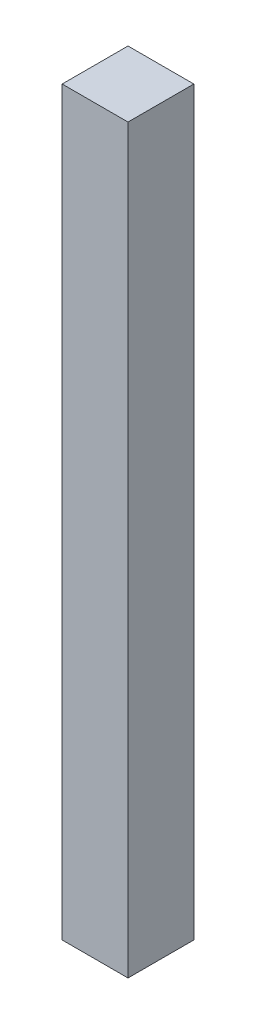
SolidWorks part; units mm, degrees
ref_plane "Front Plane" through (0, 0, 0) normal (0, 0, 1) x (1, 0, 0)
ref_plane "Top Plane" through (0, 0, 0) normal (0, 1, 0) x (1, 0, 0)
ref_plane "Right Plane" through (0, 0, 0) normal (1, 0, 0) x (0, 0, -1)
sketch "Sketch1" plane through (0, 0, 0) normal (0, 1, 0) x (1, 0, 0)
  line L1 (0, 0) -> (25.4, 0)
  line L2 (0, 0) -> (0, 25.4)
  line L3 (0, 25.4) -> (25.4, 25.4)
  line L4 (25.4, 0) -> (25.4, 25.4)
  dimension "D1" = 25.4
  dimension "D2" = 25.4
extrude "Boss-Extrude1" add sketch "Sketch1" along normal blind 609.6
sketch "Sketch3" plane through (0, 0, -25.4) normal (0, 0, -1) x (-1, 0, 0)
  line L0 (0, 609.6) -> (0, 0) construction
  line L1 (0, 466.3042) -> (-25.4, 466.3042)
  line L2 (0, 466.3042) -> (0, 609.6)
  line L3 (0, 609.6) -> (-25.4, 609.6)
  line L4 (-25.4, 466.3042) -> (-25.4, 609.6)
  line L6 (-25.4, 466.3042) -> (0, 466.3042) construction
extrude "Cut-Extrude1" [suppressed] cut sketch "Sketch3" against normal up to surface (25.4 mm away) up to face at (12.7, 304.8, 0)
sketch "Sketch4" [suppressed] plane through (0, 0, 0) normal (0, 0, 1) x (1, 0, 0)
  line L0 (0, 609.6) -> (0, 0) construction
  line L1 (0, 276.4933) -> (25.4, 276.4933)
  line L2 (0, 276.4933) -> (0, 609.6)
  line L3 (0, 609.6) -> (25.4, 609.6)
  line L4 (25.4, 276.4933) -> (25.4, 609.6)
  line L6 (0, 276.4933) -> (25.4, 276.4933) construction
extrude "Cut-Extrude2" [suppressed] cut sketch "Sketch4" against normal up to surface (430.6021 mm away) up to face at (12.7, 304.8, -25.4)
sketch "Sketch5" plane through (0, 0, -25.4) normal (0, 0, -1) x (-1, 0, 0)
  line L0 (0, 609.6) -> (0, 0) construction
  line L1 (0, 571.9407) -> (-25.4, 571.9407)
  line L2 (0, 571.9407) -> (0, 609.6)
  line L3 (0, 609.6) -> (-25.4, 609.6)
  line L4 (-25.4, 571.9407) -> (-25.4, 609.6)
extrude "Cut-Extrude3" cut sketch "Sketch5" against normal up to surface (25.4 mm away) up to face at (12.7, 304.8, 0)
sketch "Sketch6" [suppressed] plane through (0, 0, -25.4) normal (0, 0, -1) x (-1, 0, 0)
  line L0 (0, 609.6) -> (0, 0) construction
  line L1 (0, 553.696) -> (-25.4, 553.696)
  line L2 (0, 553.696) -> (0, 609.6)
  line L3 (0, 609.6) -> (-25.4, 609.6)
  line L4 (-25.4, 553.696) -> (-25.4, 609.6)
  line L6 (-25.4, 553.696) -> (0, 553.696) construction
extrude "Cut-Extrude4" [suppressed] cut sketch "Sketch6" against normal up to surface (25.4 mm away) up to face at (12.7, 285.9703, 0)
sketch "Sketch7" [suppressed] plane through (0, 0, 0) normal (0, 0, 1) x (1, 0, 0)
  line L0 (25.4, 609.6) -> (25.4, 0) construction
  line L1 (25.4, 422.1079) -> (0, 422.1079)
  line L2 (25.4, 422.1079) -> (25.4, 609.6)
  line L3 (25.4, 609.6) -> (0, 609.6)
  line L4 (0, 422.1079) -> (0, 609.6)
  line L8 (0, 422.1079) -> (25.4, 422.1079) construction
extrude "Cut-Extrude5" [suppressed] cut sketch "Sketch7" against normal up to surface (25.4 mm away) up to face at (12.7, 285.9703, -25.4)
sketch "Sketch8" [suppressed] plane through (0, 0, -25.4) normal (0, 0, -1) x (-1, 0, 0)
  line L0 (0, 609.6) -> (0, 0) construction
  line L1 (0, 319.3022) -> (-25.4, 319.3022)
  line L2 (0, 319.3022) -> (0, 609.6)
  line L3 (0, 609.6) -> (-25.4, 609.6)
  line L4 (-25.4, 319.3022) -> (-25.4, 609.6)
  line L6 (-25.4, 319.3022) -> (0, 319.3022) construction
extrude "Cut-Extrude6" [suppressed] cut sketch "Sketch8" against normal up to surface (25.4 mm away) up to face at (12.7, 285.9703, 0)
sketch "Sketch9" [suppressed] plane through (0, 0, 0) normal (0, 0, 1) x (1, 0, 0)
  line L0 (0, 609.6) -> (0, 0) construction
  line L1 (0, 329.8783) -> (25.4, 329.8783)
  line L2 (0, 329.8783) -> (0, 609.6)
  line L3 (0, 609.6) -> (25.4, 609.6)
  line L4 (25.4, 329.8783) -> (25.4, 609.6)
  line L6 (0, 329.8783) -> (25.4, 329.8783) construction
extrude "Cut-Extrude7" [suppressed] cut sketch "Sketch9" against normal up to surface (25.4 mm away) up to face at (12.7, 285.9703, -25.4)
sketch "Sketch10" [suppressed] plane through (25.4, 0, 0) normal (1, 0, 0) x (0, 0, -1)
  line L1 (25.4, 329.8783) -> (0, 329.8783)
  line L2 (25.4, 329.8783) -> (25.4, 0)
  line L3 (25.4, 0) -> (0, 0)
  line L4 (0, 329.8783) -> (0, 0)
extrude "Boss-Extrude2" [suppressed] add sketch "Sketch10" along normal blind 25.4
sketch "Sketch11" [suppressed] plane through (0, 0, -25.4) normal (0, 0, -1) x (-1, 0, 0)
  line L1 (0, 329.8783) -> (-50.8, 329.8783)
  line L2 (0, 329.8783) -> (0, 0)
  line L3 (0, 0) -> (-50.8, 0)
  line L4 (-50.8, 329.8783) -> (-50.8, 0)
extrude "Boss-Extrude3" [suppressed] add sketch "Sketch11" along normal blind 25.4
sketch "Sketch12" [suppressed] plane through (0, 0, 0) normal (0, 0, 1) x (1, 0, 0)
  line L1 (25.4, 319.3022) -> (0, 319.3022)
  line L2 (25.4, 319.3022) -> (25.4, 0)
  line L3 (25.4, 0) -> (0, 0)
  line L4 (0, 319.3022) -> (0, 0)
extrude "Boss-Extrude4" [suppressed] add sketch "Sketch12" along normal blind 25.4
sketch "Sketch13" [suppressed] plane through (25.4, 0, 0) normal (1, 0, 0) x (0, 0, -1)
  line L0 (-25.4, 0) -> (25.4, 0) construction
  line L1 (25.4, 319.3022) -> (-25.4, 319.3022)
  line L2 (25.4, 319.3022) -> (25.4, 0)
  line L3 (25.4, 0) -> (-25.4, 0)
  line L4 (-25.4, 319.3022) -> (-25.4, 0)
  line L5 (-25.4, 0) -> (-25.4, 319.3022) construction
extrude "Boss-Extrude5" [suppressed] add sketch "Sketch13" along normal blind 25.4
sketch "Sketch14" [suppressed] plane through (0, 0, -25.4) normal (0, 0, -1) x (-1, 0, 0)
  line L0 (-25.4, 422.1079) -> (-25.4, 0) construction
  line L1 (-25.4, 422.1079) -> (0, 422.1079)
  line L2 (-25.4, 422.1079) -> (-25.4, 0)
  line L3 (-25.4, 0) -> (0, 0)
  line L4 (0, 422.1079) -> (0, 0)
extrude "Boss-Extrude6" [suppressed] add sketch "Sketch14" along normal blind 25.4
sketch "Sketch15" [suppressed] plane through (25.4, 0, 0) normal (1, 0, 0) x (0, 0, -1)
  line L1 (50.8, 422.1079) -> (0, 422.1079)
  line L2 (50.8, 422.1079) -> (50.8, 0)
  line L3 (50.8, 0) -> (0, 0)
  line L4 (0, 422.1079) -> (0, 0)
extrude "Boss-Extrude7" [suppressed] add sketch "Sketch15" along normal blind 25.4
sketch "Sketch16" plane through (0, 0, 0) normal (0, 0, 1) x (1, 0, 0)
  line L1 (25.4, 571.9407) -> (0, 571.9407)
  line L2 (25.4, 571.9407) -> (25.4, 0)
  line L3 (25.4, 0) -> (0, 0)
  line L4 (0, 571.9407) -> (0, 0)
extrude "Boss-Extrude8" add sketch "Sketch16" along normal blind 25.4
sketch "Sketch17" plane through (25.4, 0, 0) normal (1, 0, 0) x (0, 0, -1)
  line L1 (25.4, 571.9407) -> (-25.4, 571.9407)
  line L2 (25.4, 571.9407) -> (25.4, 0)
  line L3 (25.4, 0) -> (-25.4, 0)
  line L4 (-25.4, 571.9407) -> (-25.4, 0)
extrude "Boss-Extrude9" add sketch "Sketch17" along normal blind 25.4
sketch "Sketch18" [suppressed] plane through (0, 0, -25.4) normal (0, 0, -1) x (-1, 0, 0)
  line L1 (0, 276.4933) -> (-25.4, 276.4933)
  line L2 (0, 276.4933) -> (0, 0)
  line L3 (0, 0) -> (-25.4, 0)
  line L4 (-25.4, 276.4933) -> (-25.4, 0)
extrude "Boss-Extrude10" [suppressed] add sketch "Sketch18" along normal blind 25.4
sketch "Sketch19" [suppressed] plane through (25.4, 0, 0) normal (1, 0, 0) x (0, 0, -1)
  line L1 (50.8, 276.4933) -> (0, 276.4933)
  line L2 (50.8, 276.4933) -> (50.8, 0)
  line L3 (50.8, 0) -> (0, 0)
  line L4 (0, 276.4933) -> (0, 0)
extrude "Boss-Extrude11" [suppressed] add sketch "Sketch19" along normal blind 25.4
sketch "Sketch22" [suppressed] plane through (25.4, 0, 0) normal (1, 0, 0) x (0, 0, -1)
  line L1 (0, 553.696) -> (25.4, 553.696)
  line L2 (0, 553.696) -> (0, 0)
  line L3 (0, 0) -> (25.4, 0)
  line L4 (25.4, 553.696) -> (25.4, 0)
extrude "Boss-Extrude14" [suppressed] add sketch "Sketch22" along normal blind 25.4
sketch "Sketch23" [suppressed] plane through (0, 0, -25.4) normal (0, 0, -1) x (-1, 0, 0)
  line L1 (-50.8, 553.696) -> (0, 553.696)
  line L2 (-50.8, 553.696) -> (-50.8, 0)
  line L3 (-50.8, 0) -> (0, 0)
  line L4 (0, 553.696) -> (0, 0)
extrude "Boss-Extrude15" [suppressed] add sketch "Sketch23" along normal blind 25.4
sketch "Sketch24" [suppressed] plane through (0, 0, 0) normal (0, 0, 1) x (1, 0, 0)
  line L0 (25.4, 466.3042) -> (25.4, 0) construction
  line L1 (0, 466.3042) -> (25.4, 466.3042)
  line L2 (0, 466.3042) -> (0, 0)
  line L3 (0, 0) -> (25.4, 0)
  line L4 (25.4, 466.3042) -> (25.4, 0)
extrude "Boss-Extrude16" [suppressed] add sketch "Sketch24" along normal blind 25.4
sketch "Sketch25" [suppressed] plane through (25.4, 0, 0) normal (1, 0, 0) x (0, 0, -1)
  line L1 (-25.4, 0) -> (25.4, 0)
  line L2 (-25.4, 0) -> (-25.4, 466.3042)
  line L3 (-25.4, 466.3042) -> (25.4, 466.3042)
  line L4 (25.4, 0) -> (25.4, 466.3042)
extrude "Boss-Extrude17" [suppressed] add sketch "Sketch25" along normal blind 25.4
sketch "Sketch26" [suppressed] plane through (0, 329.8783, 0) normal (0, 1, 0) x (1, 0, 0)
  line L0 (0, 50.8) -> (50.8, 50.8) construction
  line L1 (50.8, 0) -> (25.4, 0)
  line L2 (50.8, 0) -> (50.8, 50.8)
  line L4 (25.4, 0) -> (25.4, 25.4)
  line L5 (0, 50.8) -> (0, 0) construction
  line L6 (50.8, 50.8) -> (0, 50.8)
  line L8 (25.4, 25.4) -> (0, 25.4)
  line L9 (0, 50.8) -> (0, 25.4)
  dimension "D1" = 25.4
  dimension "D2" = 25.4
extrude "Cut-Extrude8" [suppressed] cut sketch "Sketch26" against normal up to surface (329.8783 mm away)
sketch "Sketch27" [suppressed] plane through (0, 466.3042, 0) normal (0, 1, 0) x (1, 0, 0)
  line L1 (50.8, -25.4) -> (0, -25.4)
  line L2 (50.8, -25.4) -> (50.8, 0)
  line L3 (50.8, 0) -> (0, 0)
  line L4 (0, -25.4) -> (0, 0)
extrude "Cut-Extrude9" [suppressed] cut sketch "Sketch27" against normal up to surface (466.3042 mm away)
sketch "Sketch28" [suppressed] plane through (0, 276.4933, 0) normal (0, 1, 0) x (1, 0, 0)
  line L0 (0, 50.8) -> (0, 0) construction
  line L1 (50.8, 50.8) -> (0, 50.8)
  line L2 (50.8, 50.8) -> (50.8, 25.4)
  line L3 (50.8, 25.4) -> (0, 25.4)
  line L4 (0, 50.8) -> (0, 25.4)
extrude "Cut-Extrude10" [suppressed] cut sketch "Sketch28" against normal up to surface (276.4933 mm away)
sketch "Sketch29" [suppressed] plane through (0, 553.696, 0) normal (0, 1, 0) x (1, 0, 0)
  line L0 (0, 0) -> (0, 50.8) construction
  line L1 (50.8, 50.8) -> (0, 50.8)
  line L2 (50.8, 50.8) -> (50.8, 25.4)
  line L3 (50.8, 25.4) -> (0, 25.4)
  line L4 (0, 50.8) -> (0, 25.4)
extrude "Cut-Extrude11" [suppressed] cut sketch "Sketch29" against normal up to surface (553.696 mm away)
sketch "Sketch30" [suppressed] plane through (0, 0, -25.4) normal (0, 0, -1) x (-1, 0, 0)
  line L1 (-50.8, 276.4933) -> (0, 276.4933)
  line L2 (-50.8, 276.4933) -> (-50.8, 0)
  line L3 (-50.8, 0) -> (0, 0)
  line L4 (0, 276.4933) -> (0, 0)
extrude "Boss-Extrude18" [suppressed] add sketch "Sketch30" along normal blind 25.4
sketch "Sketch31" [suppressed] plane through (0, 276.4933, 0) normal (0, 1, 0) x (1, 0, 0)
  line L0 (0, 50.8) -> (0, 0) construction
  line L1 (50.8, 50.8) -> (0, 50.8)
  line L2 (50.8, 50.8) -> (50.8, 25.4)
  line L3 (50.8, 25.4) -> (0, 25.4)
  line L4 (0, 50.8) -> (0, 25.4)
extrude "Cut-Extrude12" [suppressed] cut sketch "Sketch31" against normal up to surface (276.4933 mm away)
sketch "Sketch32" [suppressed] plane through (0, 0, -25.4) normal (0, 0, -1) x (-1, 0, 0)
  line L1 (0, 276.4933) -> (-50.8, 276.4933)
  line L2 (0, 276.4933) -> (0, 0)
  line L3 (0, 0) -> (-50.8, 0)
  line L4 (-50.8, 276.4933) -> (-50.8, 0)
extrude "Boss-Extrude19" [suppressed] add sketch "Sketch32" along normal blind 25.4
